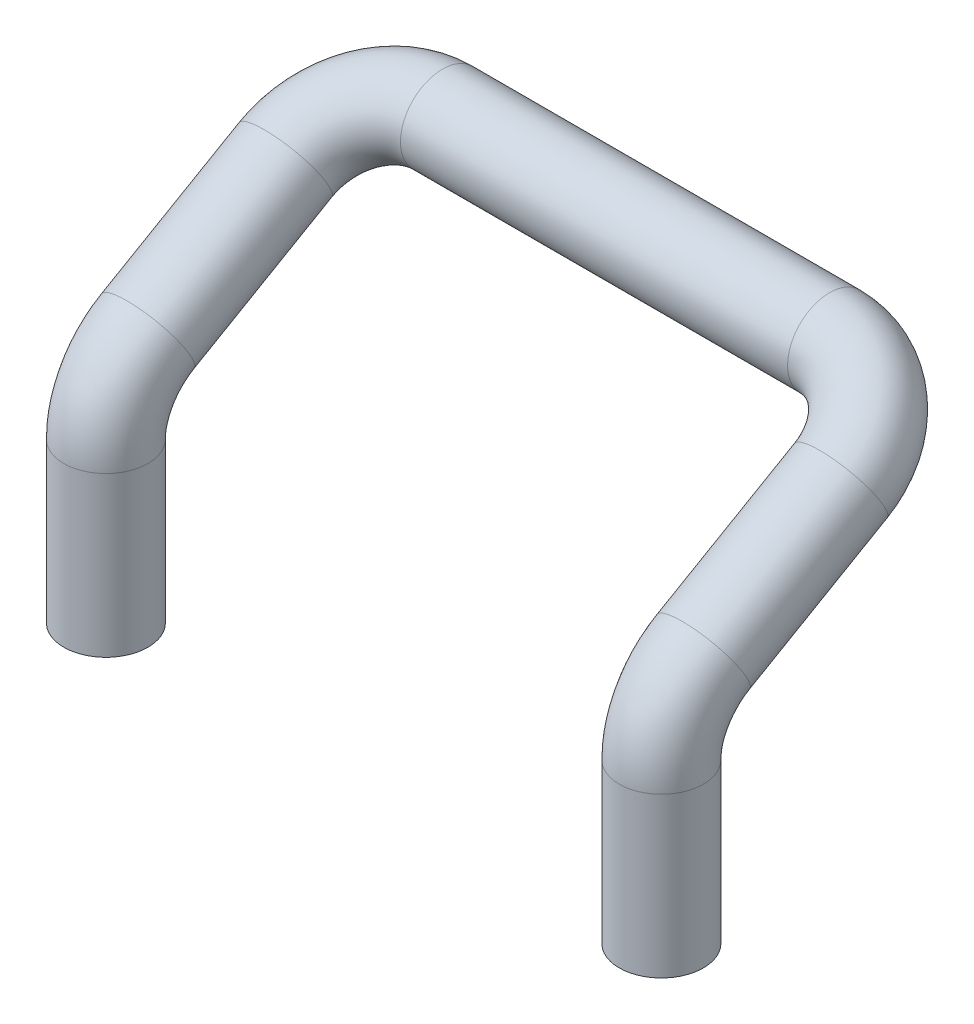
SolidWorks part; units mm, degrees
ref_plane "Front Plane" through (0, 0, 0) normal (0, 0, 1) x (1, 0, 0)
ref_plane "Top Plane" through (0, 0, 0) normal (0, 1, 0) x (1, 0, 0)
ref_plane "Right Plane" through (0, 0, 0) normal (1, 0, 0) x (0, 0, -1)
ref_axis "Axis_X" through (-8.8, 0, 0) along (1, 0, 0)
ref_axis "Axis_Y" through (0, 49.35, 0) along (0, -1, 0)
ref_axis "Axis_Z" through (0, 0, 0) along (0, 0, 1)
ref_plane "Plane1" through (66, 0, 0) normal (1, 0, 0) x (0, 0, -1)
sketch3d "3DSketch1"
  line L0 (0, 0, 0) -> (0, 18.91, 0)
  line L1 (0, 27.5709, -5.001) -> (0, 37.001, -21.3391)
  line L2 (10, 42, -30) -> (56, 42, -30)
  line L3 (66, 37.001, -21.3391) -> (66, 27.5709, -5.001)
  line L4 (66, 18.91, 0) -> (66, 0, 0)
  arc A0 (66, 18.91, 0) -> (66, 27.5709, -5.001) centre (66, 18.91, -10) ccw
  arc A1 (66, 37.001, -21.3391) -> (56, 42, -30) centre (56, 37.001, -21.3391) ccw
  arc A2 (0, 37.001, -21.3391) -> (10, 42, -30) centre (10, 37.001, -21.3391) ccw
  arc A3 (0, 18.91, 0) -> (0, 27.5709, -5.001) centre (0, 18.91, -10) ccw
  point P10 (56, 18.91, -10)
  point P13 (66, 42, -30)
  point P15 (56, 45.6619, -16.3402)
  point P18 (0, 42, -30)
  point P19 (10, 28.3402, -26.3381)
  point P23 (-10, 18.91, -10)
  dimension "KSS_3" = 30
  dimension "FIX_2" = 10
  dimension "L" = 66
  dimension "KSS_4" = 42
  dimension "MSM_1" = 18.91
sketch "Sketch2" plane through (0, 0, 0) normal (0, 1, 0) x (1, 0, 0)
  circle A0 centre (0, 0) radius 5
  dimension "D" = 10
sweep "Sweep1" add profiles "Sketch2" path "3DSketch1"
hole_wizard "Tap1" positions "Sketch4" profile "Sketch3" hole size "M4x0.7" standard "JIS"
sketch "Sketch4" plane through (0, 0, 0) normal (0, -1, 0) x (-1, 0, 0)
  point P0 (0, 0)
  point P3 (-66, 0)
sketch "Sketch3" plane through (0, 0, 0) normal (1, 0, 0) x (0, 0, -1)
  line L0 (0, 0) -> (0, 16.242)
  line L1 (0, 16.242) -> (2.067, 15)
  line L2 (2.067, 15) -> (2.067, 0)
  line L5 (2.067, 0) -> (0, 0)
  line L10 (0, 16.242) -> (-2.067, 15) construction
  line L11 (0, -6.35) -> (0, 107.95) construction
  dimension "HSD_1" = 4.134
  dimension "KSS_1" = 15
  dimension "Drill Angle" = 118
cosmetic thread "Thread1" parameters "D_s"=13, "M"=5
cosmetic thread "Thread2" parameters "D_s"=13, "M"=5
equation "\"KSS_1@Sketch3\"= \"D_s@Thread1\" + 2"
equation "\"A\"=40"
equation "\"H\"=47"
equation "\"KSS_3@3DSketch1\"= \"A\" - \"D@Sketch2\""
equation "\"KSS_4@3DSketch1\"= \"H\" - \"D@Sketch2\" / 2"
equation "\"L\"=66.000000"
equation "\"KSS_2@Plane1\" = \"L\""
